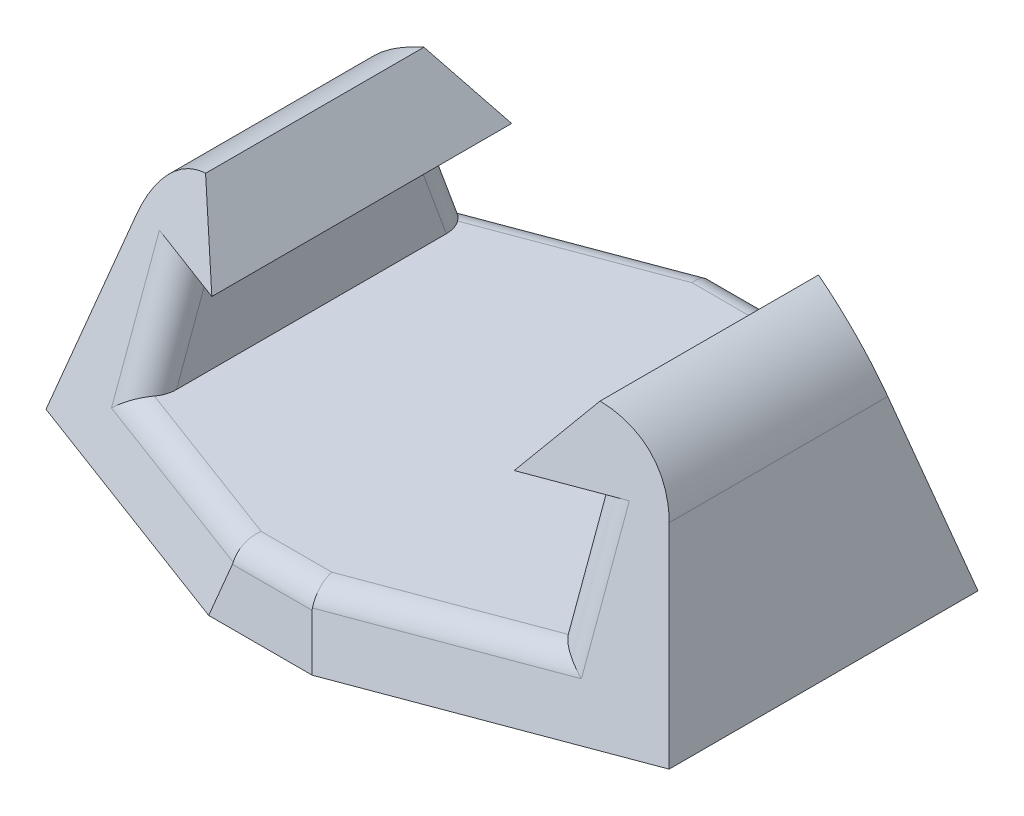
SolidWorks part; units mm, degrees
ref_plane "前基準面" through (0, 0, 0) normal (0, 0, 1) x (1, 0, 0)
ref_plane "上基準面" through (0, 0, 0) normal (0, 1, 0) x (1, 0, 0)
ref_plane "右基準面" through (0, 0, 0) normal (1, 0, 0) x (0, 0, -1)
sketch "草圖2" plane through (0, 0, 0) normal (0, 0, 1) x (1, 0, 0)
  line L2 (-8.1955, 3.6785) -> (-10.1955, 3.6785)
  line L3 (-10.1955, 3.6785) -> (-10.1955, -0.8215)
  line L4 (-10.1955, -0.8215) -> (5.8045, -0.8215)
  line L5 (5.8045, -0.8215) -> (5.8045, 3.6785)
  line L6 (5.8045, 3.6785) -> (3.8045, 3.6785)
  line L9 (7.6185, 6.1785) -> (10.164, -3.3215)
  line L10 (10.164, -3.3215) -> (-14.6095, -3.3215)
  line L11 (-14.6095, -3.3215) -> (-12.064, 6.1785)
  line L12 (-12.064, 6.1785) -> (-10.064, 6.1785)
  line L13 (-10.064, 6.1785) -> (-8.1955, 3.6785)
  line L14 (3.8045, 3.6785) -> (5.6185, 6.1785)
  line L15 (5.6185, 6.1785) -> (7.6185, 6.1785)
  dimension "D2" = 2
  dimension "D3" = 2
  dimension "D4" = 2
  dimension "D5" = 4.5
  dimension "D6" = 2.5
  dimension "D7" = 53.226
  dimension "D8" = 16
  dimension "D9" = 75
  dimension "D10" = 75
  dimension "D11" = 2
  dimension "D12" = 54.035
extrude "填料-伸長1" add sketch "草圖2" along normal blind 20
sketch "草圖3" plane through (0, 0, 0) normal (1, 0, 0) x (0, 0, -1)
  line L0 (-20, -3.3215) -> (-17.4545, 6.1785)
  line L1 (-20, 6.1785) -> (0, 6.1785) construction
  line L2 (-17.4545, 6.1785) -> (-20, 6.1785)
  line L3 (-20, 6.1785) -> (-20, -3.3215)
  line L4 (0, 6.1785) -> (-2.5455, 6.1785)
  line L5 (-2.5455, 6.1785) -> (0, -3.3215)
  line L6 (0, -3.3215) -> (0, 6.1785)
  dimension "D1" = 15
  dimension "D2" = 15
extrude "除料-伸長1" cut sketch "草圖3" against normal through all and the other way through all
fillet "圓角1" radius 4 2 edges at (7.6185, 6.1785, 10) (-12.064, 6.1785, 10)
chamfer "導角1" distance 10 angle 20 4 edges at (9.2673, 0.0249, 0.8967) (-13.7128, 0.0249, 0.8967) (-13.7128, 0.0249, 19.1033) (9.2673, 0.0249, 19.1033)
fillet "圓角2" radius 1 10 edges at (-6.9028, -0.8215, 18.0989) (-2.2228, -0.8215, 19.3301) (2.4845, -0.8215, 18.0887) (-6.9028, -0.8215, 1.9011) (-2.2228, -0.8215, 0.6699) (2.4845, -0.8215, 1.9113) (-10.1955, 1.4285, 3.9607) (5.8045, 1.4285, 3.981) (5.8045, 1.4285, 16.019) (-10.1955, 1.4285, 16.0393)
